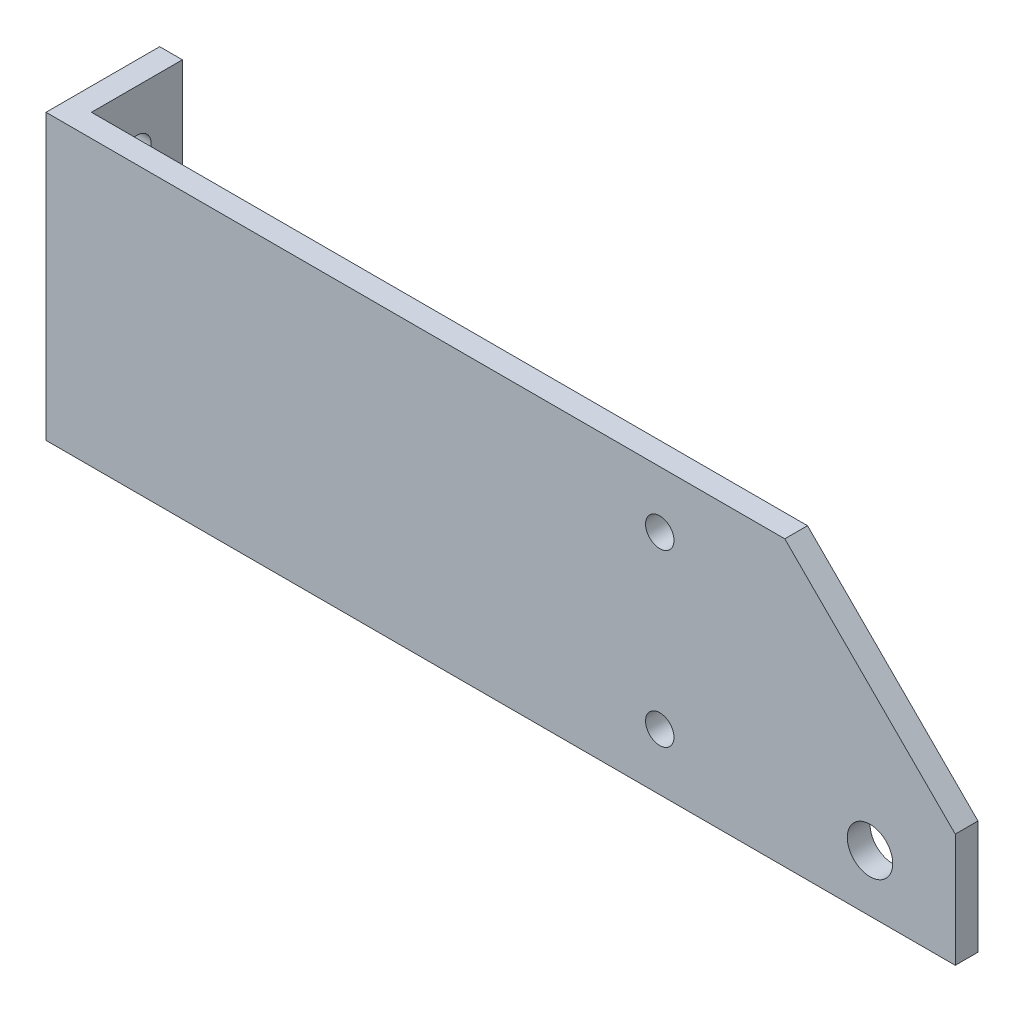
SolidWorks part; units mm, degrees
ref_plane "Спереди" through (0, 0, 0) normal (0, 0, 1) x (1, 0, 0)
ref_plane "Сверху" through (0, 0, 0) normal (0, 1, 0) x (1, 0, 0)
ref_plane "Справа" through (0, 0, 0) normal (1, 0, 0) x (0, 0, -1)
sketch "Эскиз1" plane through (0, 0, 0) normal (0, 1, 0) x (1, 0, 0)
  line L1 (0, 0) -> (160, 0)
  line L2 (0, 0) -> (0, 4)
  line L3 (4, 4) -> (160, 4)
  line L4 (160, 0) -> (160, 4)
  line L6 (0, 4) -> (0, 20)
  line L7 (0, 20) -> (4, 20)
  line L8 (4, 4) -> (4, 20)
  dimension "D1" = 160
  dimension "D2" = 4
  dimension "D3" = 20
  dimension "D4" = 4
extrude "Бобышка-Вытянуть1" add sketch "Эскиз1" along normal blind 50
sketch "Эскиз2" plane through (0, 0, 0) normal (-1, 0, 0) x (0, 0, 1)
  line L0 (-12, 44.9311) -> (-12, 11.555) construction
  line L1 (-20, 50) -> (0, 50) construction
  line L3 (0, 50) -> (0, 0) construction
  circle A0 centre (-12, 40) radius 2.5
  circle A1 centre (-12, 10) radius 2.5
  dimension "D2" = 5
  dimension "D3" = 5
  dimension "D1" = 12
  dimension "D4" = 30
  dimension "D5" = 10
extrude "Вырез-Вытянуть1" cut sketch "Эскиз2" against normal blind 10
sketch "Эскиз3" plane through (0, 0, 0) normal (0, 0, 1) x (1, 0, 0)
  line L0 (108, 46.6766) -> (108, 6.7064) construction
  line L1 (160, 50) -> (160, 0) construction
  line L2 (0, 50) -> (0, 0) construction
  line L5 (0, 50) -> (160, 50) construction
  circle A0 centre (108, 40) radius 2.5
  circle A1 centre (108, 10) radius 2.5
  circle A2 centre (145, 10) radius 4
  dimension "D2" = 5
  dimension "D3" = 5
  dimension "D6" = 8
  dimension "D1" = 108
  dimension "D4" = 30
  dimension "D5" = 10
  dimension "D7" = 15
extrude "Вырез-Вытянуть2" cut sketch "Эскиз3" against normal blind 10
sketch "Эскиз4" plane through (0, 0, 0) normal (0, 0, 1) x (1, 0, 0)
  line L0 (160, 20) -> (130, 50)
  line L1 (160, 50) -> (160, 0) construction
  line L2 (0, 50) -> (160, 50) construction
  line L3 (130, 50) -> (160, 50)
  line L4 (160, 50) -> (160, 20)
  dimension "D1" = 30
  dimension "D2" = 30
extrude "Вырез-Вытянуть3" cut sketch "Эскиз4" against normal blind 10
